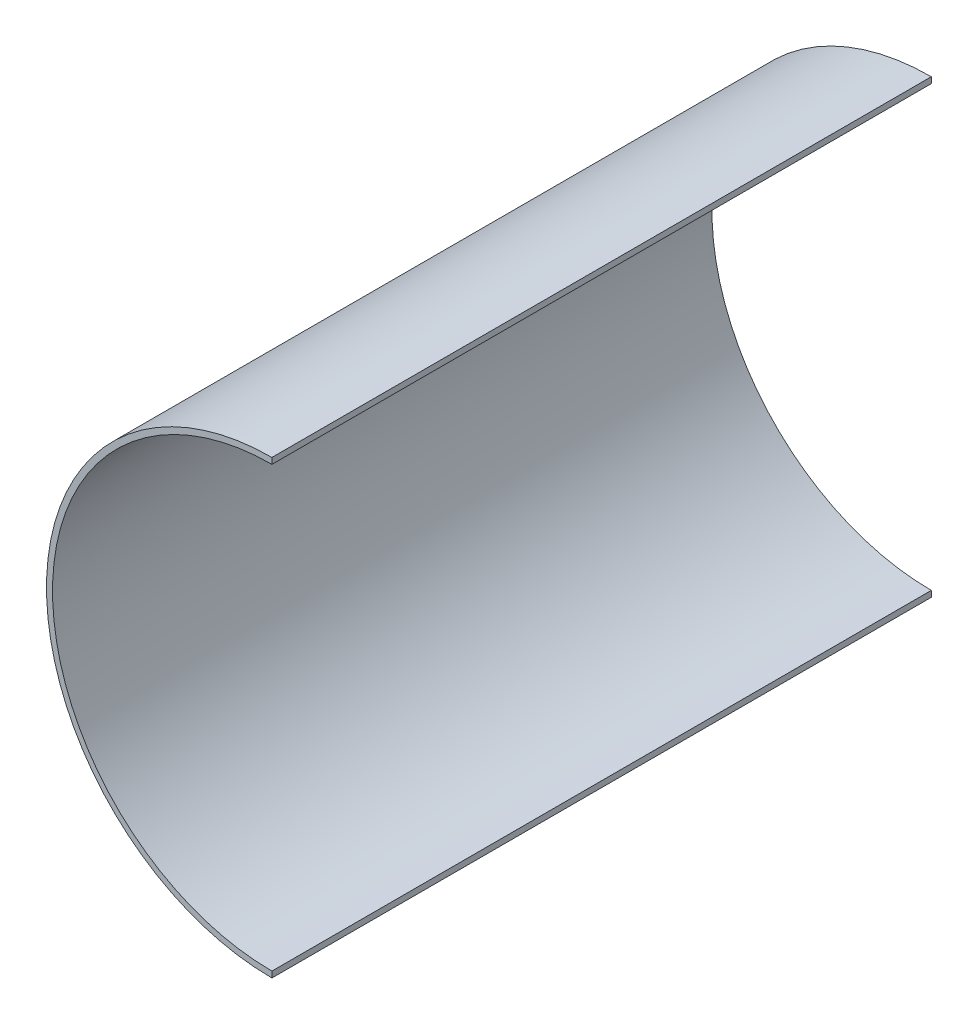
SolidWorks part; units mm, degrees
material "Fibra di Carbonio"
ref_plane "Piano frontale" through (0, 0, 0) normal (0, 0, 1) x (1, 0, 0)
ref_plane "Piano superiore" through (0, 0, 0) normal (0, 1, 0) x (1, 0, 0)
ref_plane "Piano destro" through (0, 0, 0) normal (1, 0, 0) x (0, 0, -1)
sketch "Schizzo1" plane through (0, 0, 0) normal (0, 0, 1) x (1, 0, 0)
  circle A0 centre (0, 0) radius 75
  dimension "D1" = 150
extrude "Estrusione-Sottile1" add sketch "Schizzo1" against normal up to surface (219.385 mm away) from surface thin
ref_plane "Piano1" through (-75, 0, 0) normal (-1, 0, 0) x (0, 0, 1)
hole_wizard "Foro svasato per Vite M6-1" [suppressed] positions "Schizzo3" profile "Schizzo4" countersink size "M6" standard "ISO"
sketch "Schizzo3" plane through (-75, 0, 0) normal (-1, 0, 0) x (0, 0, 1)
  point P0 (19, 0)
  dimension "D1" = 19
sketch "Schizzo4" plane through (-75, 0, 15) normal (0, 1, 0) x (0, 0, 1)
  line L0 (0, 0) -> (0, 74.999)
  line L1 (0, 74.999) -> (3.3, 74.999)
  line L2 (3.3, 74.999) -> (3.3, 3)
  line L3 (3.3, 3) -> (6.3, 0)
  line L5 (6.3, 0) -> (0, 0)
  line L6 (-3.3, 3) -> (-6.3, 0) construction
  line L10 (0, 74.999) -> (-3.3, 74.999) construction
  line L11 (0, -6.35) -> (0, 107.95) construction
  dimension "Hole Dia." = 6.6
  dimension "Hole Depth" = 74.999
  dimension "Near C'Sink Dia." = 12.6
  dimension "Near C'Sink Angle" = 90
  dimension "Drill Angle" = 180
pattern_circular "RipetizioneCircolare1" [suppressed] count 10 over 360
sketch3d "Schizzo3D2" [suppressed]
  line L0 (-75, 0, 0) -> (-75, 0, 21)
  line L1 (0, 0, 0) -> (0, 0, 36.4754) construction
  circle A0 centre (0, 0, 0) radius 75 construction
  point P0 (-75, 0, 0)
  point P4 (0, 0, 75)
  dimension "D1" = 21
sketch "Schizzo5" plane through (0, 0, 235.9367) normal (0, 0, 1) x (1, 0, 0)
  line L0 (0, -90) -> (0, 90)
  line L1 (0, 90) -> (100, 90)
  line L2 (100, 90) -> (100, -90)
  line L3 (100, -90) -> (0, -90)
  point P5 (0, 0)
  dimension "D1" = 100
  dimension "D2" = 180
extrude "Taglio-Estrusione1" cut sketch "Schizzo5" against normal blind 391
